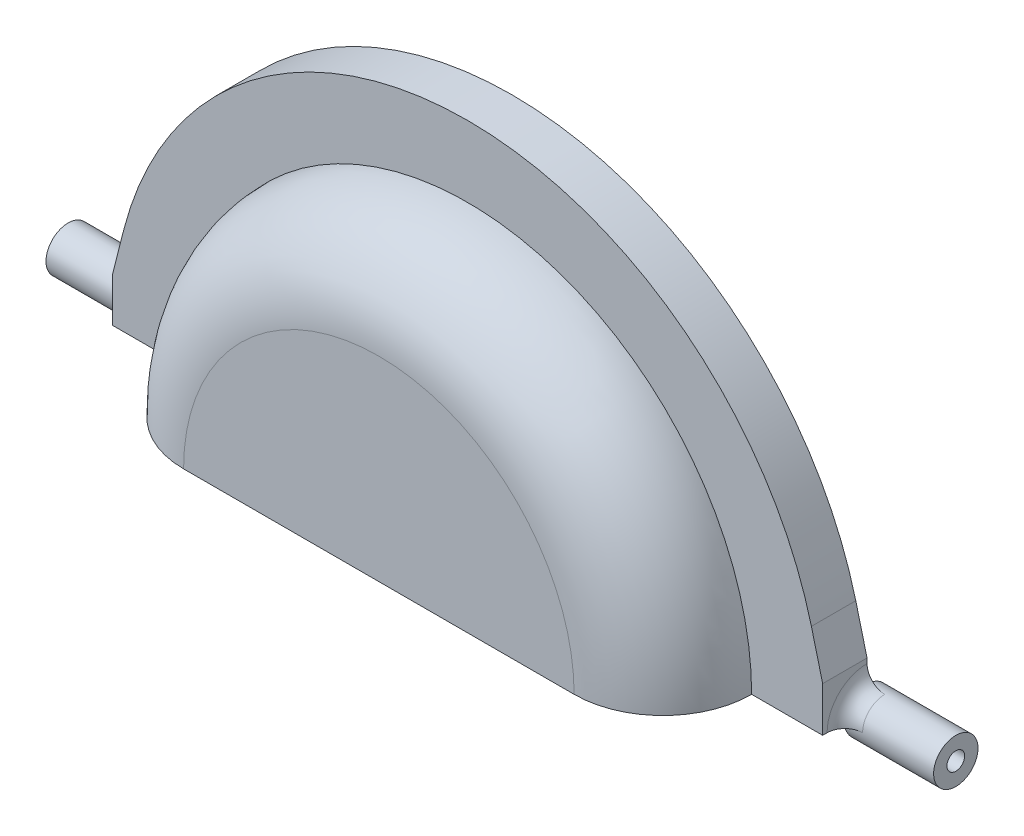
SolidWorks part; units mm, degrees
ref_plane "Front Plane" through (0, 0, 0) normal (0, 0, 1) x (1, 0, 0)
ref_plane "Top Plane" through (0, 0, 0) normal (0, 1, 0) x (1, 0, 0)
ref_plane "Right Plane" through (0, 0, 0) normal (1, 0, 0) x (0, 0, -1)
sketch "Sketch1" plane through (0, 0, 0) normal (0, 0, 1) x (1, 0, 0)
  circle A0 centre (0, 0) radius 32
extrude "Boss-Extrude1" add sketch "Sketch1" along normal blind 15 contours A0
fillet "Fillet1" radius 10 1 edges at (32, 0, 15)
shell "Shell1" thickness 2 removed face at (32, 0, 0)
sketch "Sketch2" plane through (0, 0, 0) normal (0, 0, -1) x (-1, 0, 0)
  line L0 (-55, -4.9501) -> (-40, -4.9501)
  line L1 (-60, 10) -> (-38.7298, 10)
  line L2 (-60, 10) -> (-60, -10)
  line L3 (-60, -10) -> (-38.7298, -10)
  line L4 (60, 10) -> (60, -10)
  line L7 (-55, -4.9501) -> (-55, 5.0499)
  line L8 (-40, -4.9501) -> (-40, 5.0499)
  line L9 (-55, 5.0499) -> (-40, 5.0499)
  line L10 (-55, -4.9501) -> (-40, 5.0499) construction
  line L11 (-40, -4.9501) -> (-55, 5.0499) construction
  line L12 (55, -5) -> (40, -5)
  line L13 (55, -5) -> (55, 5)
  line L14 (40, -5) -> (40, 5)
  line L15 (55, 5) -> (40, 5)
  line L16 (55, -5) -> (40, 5) construction
  line L17 (40, -5) -> (55, 5) construction
  line L18 (38.7298, 10) -> (60, 10)
  line L21 (38.7298, -10) -> (60, -10)
  arc A0 (38.7298, 10) -> (-38.7298, 10) centre (0, 0) ccw
  arc A1 (-38.7298, -10) -> (38.7298, -10) centre (0, 0) ccw
  point P8 (-47.5, 0.0499)
  point P9 (47.5, 0)
  dimension "D1" = 120
  dimension "D2" = 20
  dimension "D3" = 15
  dimension "D4" = 15
  dimension "D5" = 10
  dimension "D6" = 10
  dimension "D7" = 40
  dimension "D8" = 5
  dimension "D9" = 40
extrude "Boss-Extrude2" add sketch "Sketch2" against normal blind 5 contours L1 A0 L18 L4 L21 A1 L3 L2 | L9 L8 L0 L7 | L15 L14 L12 L13
sketch "Sketch3" plane through (0, 0, 0) normal (0, 0, -1) x (-1, 0, 0)
  circle A0 centre (0, 0) radius 29
extrude "Cut-Extrude1" cut sketch "Sketch3" against normal blind 5 contours A0
sketch "Sketch4" plane through (0, 0, 0) normal (0, 0, -1) x (-1, 0, 0)
  line L0 (-60, 0) -> (60, 0)
  line L1 (-60, 10) -> (-60, -10) construction
  line L2 (60, 10) -> (60, -10) construction
split "Split1" trim tools "Sketch4" bodies to split 103 resulting bodies 104 105
delete or keep bodies "Body-Delete1" type delete bodies bodies 104
sketch "Sketch5" plane through (-55, 0, 0) normal (1, 0, 0) x (0, 0, -1)
  circle A0 centre (0, 0) radius 1
  circle A1 centre (0, 0) radius 2.5
sketch "Sketch6" plane through (55, 0, 0) normal (-1, 0, 0) x (0, 0, 1)
  circle A0 centre (0, 0) radius 1
  circle A1 centre (0, 0) radius 2.5
extrude "Boss-Extrude3" [suppressed] add sketch "Sketch6" along normal blind 5 contours A0 | A1
extrude "Boss-Extrude4" [suppressed] add sketch "Sketch5" along normal blind 5 contours A1 | A0
sketch "Sketch7" plane through (60, 0, 0) normal (1, 0, 0) x (0, 0, -1)
  line L0 (-5, 10) -> (-5, 0) construction
  line L1 (-5, 10) -> (3.5, 10)
  line L2 (-5, 10) -> (-5, -3.5)
  line L3 (-5, -3.5) -> (3.5, -3.5)
  line L4 (3.5, 10) -> (3.5, -3.5)
  line L5 (-5, 32) -> (-5, 0) construction
  dimension "D1" = 3.5
  dimension "D2" = 3.5
sketch "Sketch8" plane through (-60, 0, 0) normal (-1, 0, 0) x (0, 0, 1)
  line L1 (5, 10) -> (-3.5, 10)
  line L2 (5, 10) -> (5, -3.5)
  line L3 (5, -3.5) -> (-3.5, -3.5)
  line L4 (-3.5, 10) -> (-3.5, -3.5)
extrude "Boss-Extrude5" [suppressed] add sketch "Sketch7" against normal blind 5.5 contours L4 L3 L2 L1
extrude "Boss-Extrude6" [suppressed] add sketch "Sketch8" against normal blind 5.5 contours L4 L3 L2 L1
fillet "Fillet2" [suppressed] radius 1
sketch "Sketch9" plane through (-40, 0, 0) normal (-1, 0, 0) x (0, 0, 1)
  circle A0 centre (0, 0) radius 1
  circle A1 centre (0, 0) radius 2.5
sketch "Sketch10" plane through (40, 0, 0) normal (1, 0, 0) x (0, 0, -1)
  circle A0 centre (0, 0) radius 1
  circle A1 centre (0, 0) radius 2.5
extrude "Boss-Extrude7" add sketch "Sketch10" along normal blind 10 contours A0 | A1
extrude "Boss-Extrude8" add sketch "Sketch9" along normal blind 10 contours A1 | A0
sketch "Sketch11" plane through (0, 0, 0) normal (0, 0, -1) x (-1, 0, 0)
  line L0 (-38.7298, 10) -> (-40, 5.0499)
  line L1 (-40, 5.0499) -> (-55, 5.0499)
  line L2 (-55, 0) -> (-55, 5.0499) construction
  line L3 (-55, 5.0499) -> (-40, 5.0499) construction
  line L4 (-55, 5.0499) -> (-55, 0)
  line L5 (-55, 0) -> (-60, 0)
  line L6 (-60, 0) -> (-60, 10)
  line L7 (-60, 10) -> (-38.7298, 10)
  line L8 (38.7298, 10) -> (40, 5)
  line L9 (40, 5) -> (55, 5)
  line L10 (55, 5) -> (55, 0)
  line L11 (-60, 0) -> (60, 0) construction
  line L12 (55, 0) -> (60, 0)
  line L13 (60, 0) -> (60, 10)
  line L14 (60, 10) -> (38.7298, 10)
extrude "Cut-Extrude2" cut sketch "Sketch11" against normal blind 10 contours L14 L8 L9 L10 L12 L13 | L7 L0 L1 L4 L5 L6
fillet "Fillet3" radius 2 2 edges at (40, 1.7678, 1.7678) (-40, 1.7678, 1.7678)
fillet "Fillet4" radius 1 1 edges at (40, 0, 1.75)
fillet "Fillet5" radius 1 1 edges at (-40, 0, 1.75)
